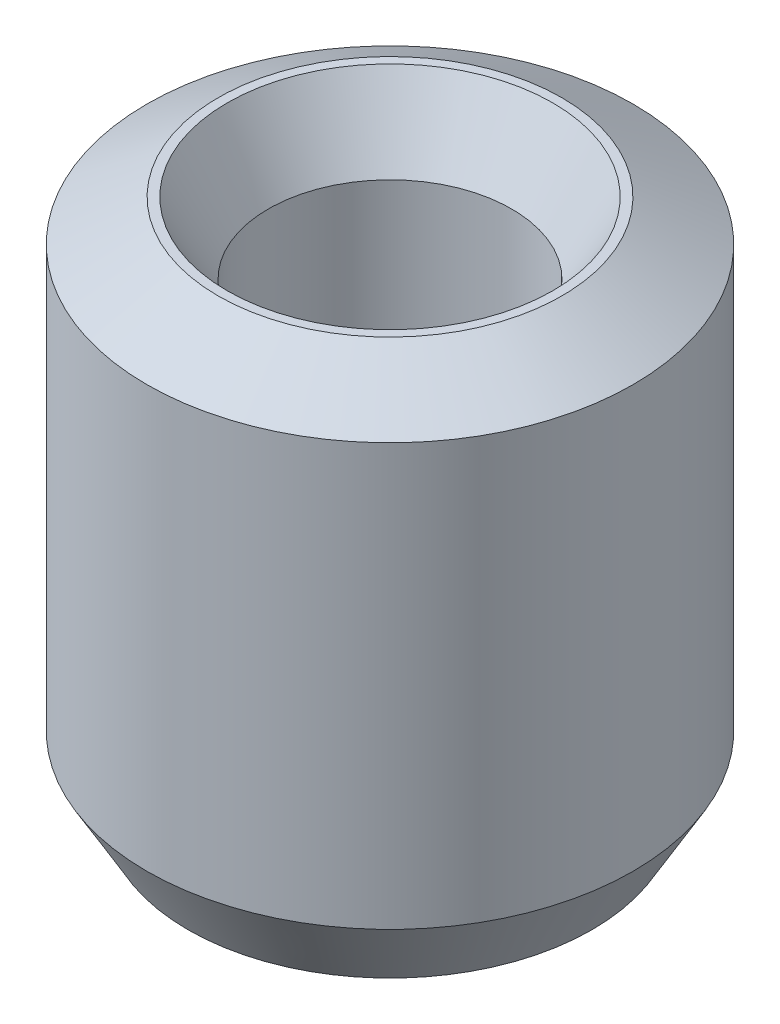
SolidWorks part; units mm, degrees
ref_plane "Front Plane" through (0, 0, 0) normal (0, 0, 1) x (1, 0, 0)
ref_plane "Top Plane" through (0, 0, 0) normal (0, 1, 0) x (1, 0, 0)
ref_plane "Right Plane" through (0, 0, 0) normal (1, 0, 0) x (0, 0, -1)
sketch "Sketch1" plane through (0, 0, 0) normal (0, 1, 0) x (1, 0, 0)
  circle A0 centre (0, 0) radius 22.5
  dimension "SLEEVE_OD" = 45
extrude "Boss-Extrude1" add sketch "Sketch1" along normal blind 49.4186
sketch "Sketch2" plane through (0, 0, 0) normal (0, 1, 0) x (1, 0, 0)
  circle A0 centre (0, 0) radius 11.2598
  dimension "BORE_D" = 22.5197
extrude "Cut-Extrude1" cut sketch "Sketch2" along normal through all
chamfer "Chamfer1" distance 3.8088 angle 60 4 edges at (0, 49.4186, 11.2598) (0, 0, 11.2598) (0, 0, 22.5) (0, 49.4186, 22.5) first distance on face at (0, 49.4186, 11.2598) first distance on face at (0, 0, 11.2598) first distance on face at (0, 49.4186, 22.5)
